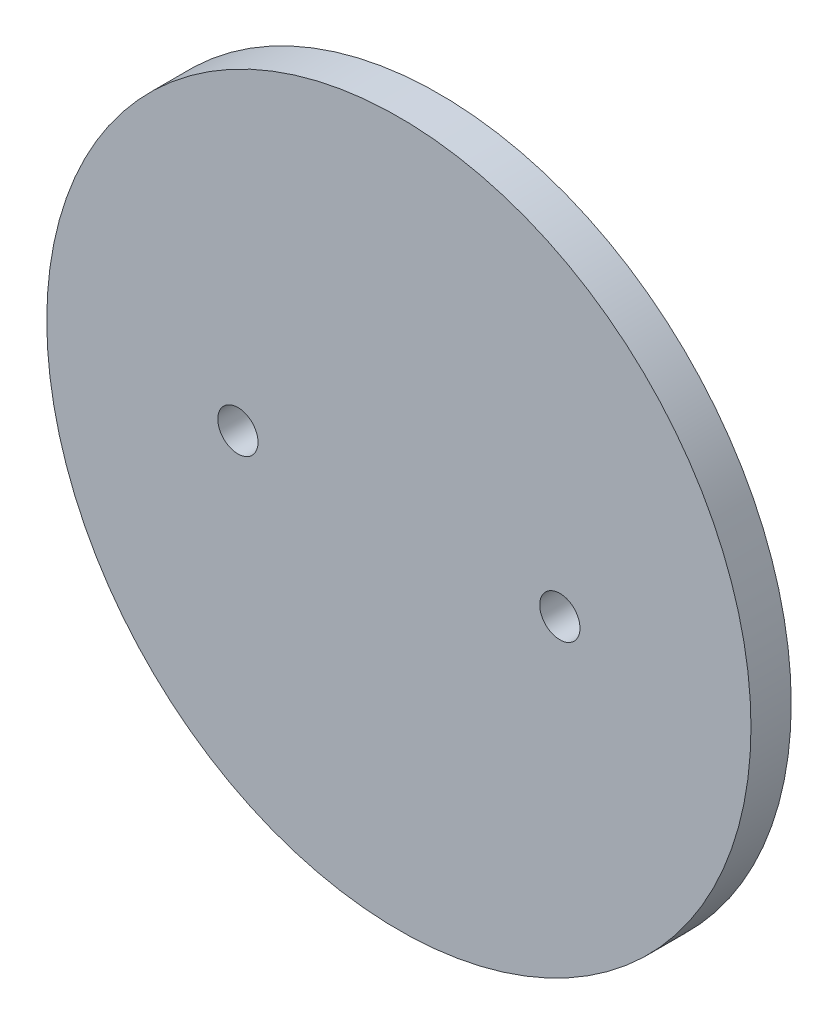
SolidWorks part; units mm, degrees
ref_plane "Front Plane" through (0, 0, 0) normal (0, 0, 1) x (1, 0, 0)
ref_plane "Top Plane" through (0, 0, 0) normal (0, 1, 0) x (1, 0, 0)
ref_plane "Right Plane" through (0, 0, 0) normal (1, 0, 0) x (0, 0, -1)
sketch "Sketch1" plane through (0, 0, 0) normal (0, 0, 1) x (1, 0, 0)
  circle A0 centre (0, 0) radius 22.225
extrude "Boss-Extrude1" add sketch "Sketch1" along normal blind 2.54
sketch "Sketch2" plane through (0, 0, 2.54) normal (0, 0, 1) x (1, 0, 0)
  line L0 (-22.225, 0) -> (22.225, 0)
  circle A0 centre (0, 0) radius 22.225 construction
  circle A1 centre (-10.16, 0) radius 1.27
  circle A2 centre (10.16, 0) radius 1.27
  point P7 (0, 0)
  dimension "D1" = 10.16
  dimension "D2" = 10.16
extrude "Cut-Extrude1" cut sketch "Sketch2" against normal through all contours L0 A1 | L0 A1 | L0 A2 | L0 A2 region at (-10.16, 0.539, 2.54) region at (10.16, 0.539, 2.54) region at (10.16, -0.539, 2.54) region at (-10.16, -0.539, 2.54)
